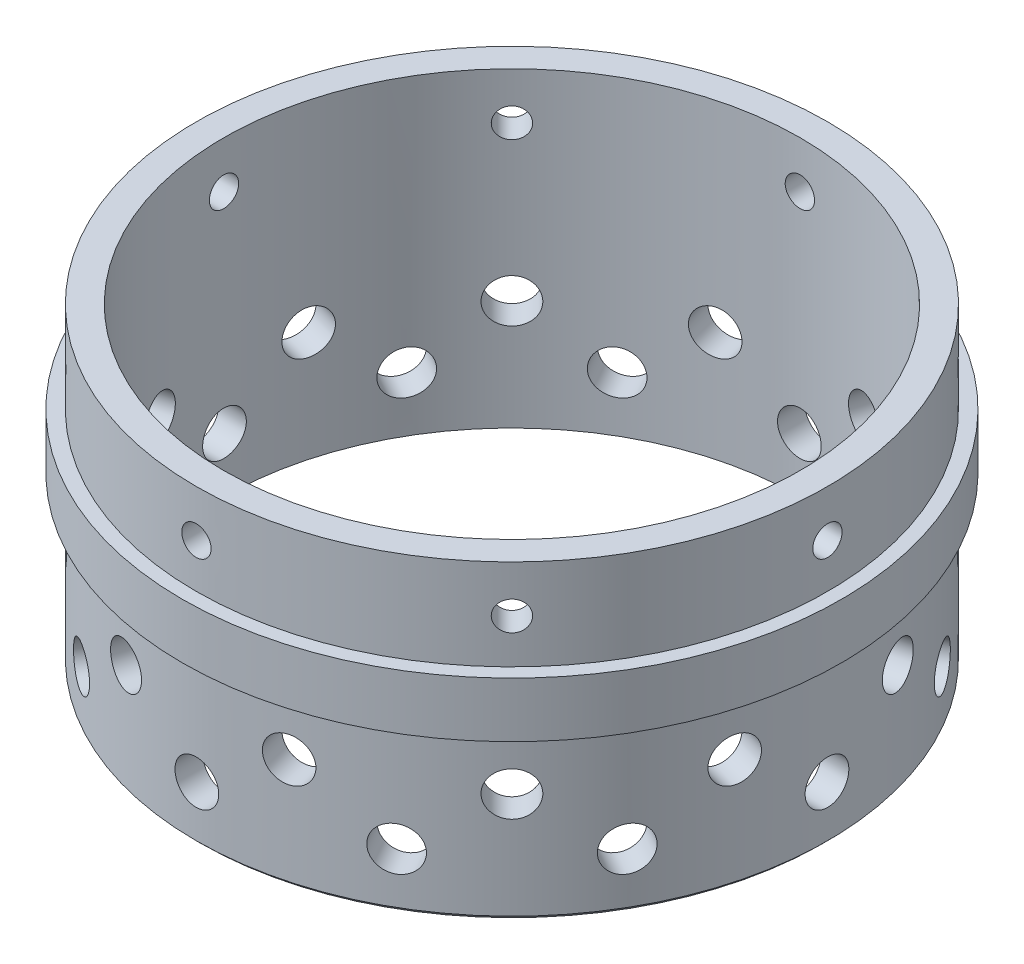
SolidWorks part; units mm, degrees
material "6061-T6 (SS)"
ref_plane "Front Plane" through (0, 0, 0) normal (0, 0, 1) x (1, 0, 0)
ref_plane "Top Plane" through (0, 0, 0) normal (0, 1, 0) x (1, 0, 0)
ref_plane "Right Plane" through (0, 0, 0) normal (1, 0, 0) x (0, 0, -1)
sketch "Sketch1" plane through (0, 0, 0) normal (0, 1, 0) x (1, 0, 0)
  circle A0 centre (0, 0) radius 66.4845
  circle A1 centre (0, 0) radius 76.0095
  circle A2 centre (0, 0) radius 72.8345
  dimension "D1" = 152.019
  dimension "D2" = 3.175
  dimension "D3" = 6.35
extrude "Boss-Extrude1" add sketch "Sketch1" along normal blind 12.7 contours A2 A0 | A1 A2 region at (-73.8596, 0, 0) region at (-70.7744, 0, 0)
extrude "Boss-Extrude2" add sketch "Sketch1<3>" against normal blind 38.1 contours A2 A0 region at (-70.7744, 0, 0)
sketch "Sketch1<3>" plane through (0, 0, 0) normal (0, 1, 0) x (1, 0, 0) same geometry as "Sketch1"
extrude "Boss-Extrude3" add sketch "Sketch1<4>" along normal blind 33.655 contours A2 A0 region at (-70.7744, 0, 0)
sketch "Sketch1<4>" plane through (0, 0, 0) normal (0, 1, 0) x (1, 0, 0) same geometry as "Sketch1"
chamfer "Chamfer1" distance 1 angle 45 1 edges at (0, -38.1, 72.8345)
sketch "Sketch2" plane through (0, 0, 0) normal (0, 0, 1) x (1, 0, 0)
  line L0 (0, 0) -> (0, 22.86) construction
  line L1 (0, 0) -> (0, -25.4) construction
  line L2 (-71.8345, -38.1) -> (71.8345, -38.1) construction
  line L3 (72.8345, 33.655) -> (-72.8345, 33.655) construction
  circle A0 centre (0, 22.86) radius 3.3782
  circle A1 centre (0, -25.4) radius 5.0419
  point P8 (0, 28.5283)
  dimension "D1" = 6.7564
  dimension "D2" = 10.0838
  dimension "D3" = 25.4
  dimension "D5" = 12.7
  dimension "D4" = 10.795
extrude "Cut-Extrude1" cut sketch "Sketch2" against normal through all contours A1 region at (0, -25.4, 0)
ref_plane "Plane1" through (-19.6727, 0, 73.4195) normal (-0.2588, 0, 0.9659) x (0, -1, 0)
sketch "Sketch3" plane through (-19.6727, 0, 73.4195) normal (-0.2588, 0, 0.9659) x (0, -1, 0)
  line L0 (12.7, 0) -> (0, 0) construction
  line L1 (38.1, -71.8345) -> (38.1, 71.8345) construction
  circle A0 centre (12.7, 0) radius 5.0419
  dimension "D3" = 25.4
  dimension "D1" = 10.0838
  dimension "D2" = 12.7
extrude "Cut-Extrude2" cut sketch "Sketch3" against normal blind 38.1
pattern_circular "CirPattern2" count 12 over 360 of "Cut-Extrude2", "Cut-Extrude1" reverse direction yes
extrude "Cut-Extrude3" cut sketch "Sketch2<3>" against normal through all contours A0
sketch "Sketch2<3>" plane through (0, 0, 0) normal (0, 0, 1) x (1, 0, 0) same geometry as "Sketch2"
pattern_circular "CirPattern3" count 8 over 360 about axis through (0, 12.7, 0) along (0, -1, 0) of "Cut-Extrude3"
equation "\"holeDia\"= 0.397in"
equation "\"D2@Sketch2\"=\"holeDia\""
equation "\"numHoles\"=12"
equation "\"D1@Plane1\"=180/\"numHoles\""
equation "\"D1@Sketch3\"=\"holeDia\""
equation "\"D1@CirPattern2\"=\"numHoles\""
